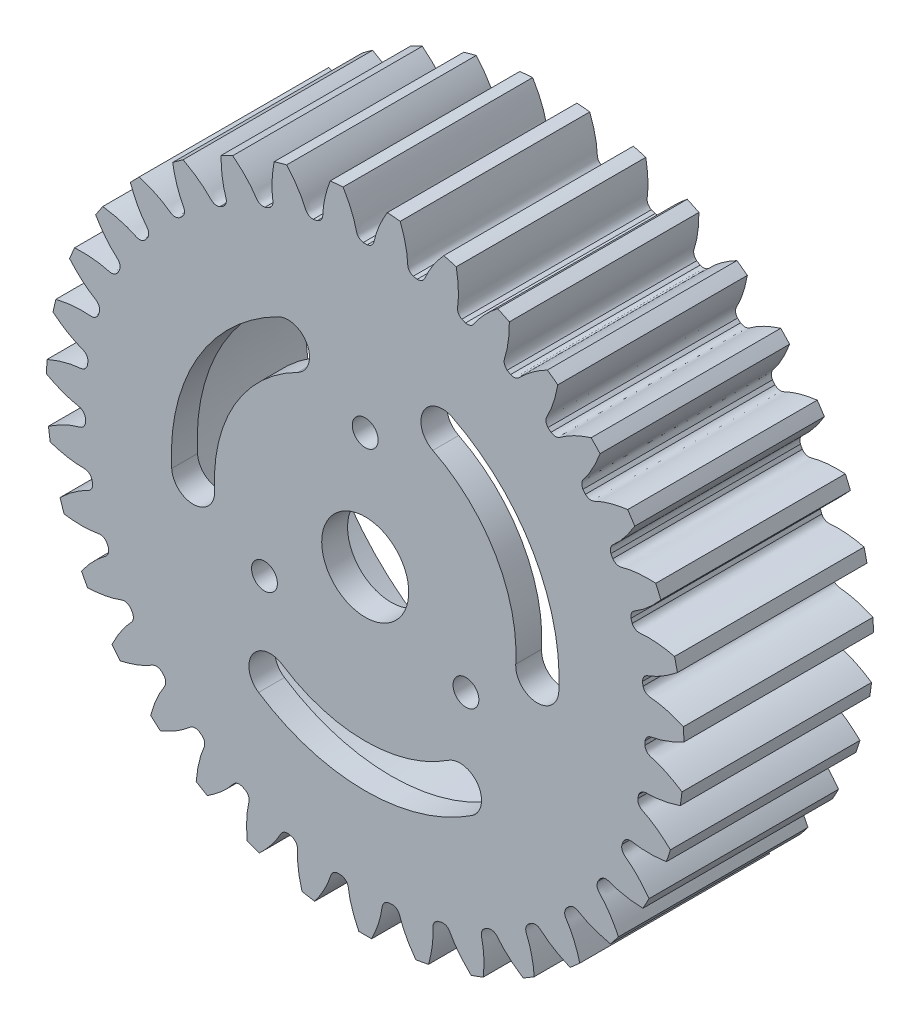
SolidWorks part; units mm, degrees
material "PLA-FC"
ref_plane "前视基准面" through (0, 0, 0) normal (0, 0, 1) x (1, 0, 0)
ref_plane "上视基准面" through (0, 0, 0) normal (0, 1, 0) x (1, 0, 0)
ref_plane "右视基准面" through (0, 0, 0) normal (1, 0, 0) x (0, 0, -1)
sketch "草图1" plane through (0, 0, 0) normal (0, 0, 1) x (1, 0, 0)
  circle A0 centre (0, 0) radius 37
extrude "凸台-拉伸1" add sketch "草图1" along normal blind 50
ref_axis "基准轴1" through (0, 0, -10.5) along (0, 0, 1)
sketch "草图2" plane through (0, 0, 0) normal (0, 0, 1) x (1, 0, 0)
  line L0 (0, 0) -> (0, 37) construction
  circle A0 centre (0, 0) radius 37 construction
  arc A1 (0.2321, 32.4992) -> (-0.2321, 32.4992) centre (0, 0) ccw
  arc A2 (7.1029, 42.1361) -> (-7.1029, 42.1361) centre (0, 0) ccw
  spline S0 degree 3 poles (0.2321, 32.4992) (0.9482, 32.6535) (1.0024, 33.1766) (1.1442, 33.7289) (1.1861, 33.8807) (1.2349, 34.0443) (1.291, 34.2194) (1.3548, 34.4057) (1.4268, 34.6031) (1.5075, 34.8114) (1.5973, 35.0301) (1.6967, 35.259) (1.8062, 35.4979) (1.9261, 35.7464) (2.057, 36.0042) (2.1991, 36.2709) (2.353, 36.5462) (2.519, 36.8297) (2.6975, 37.1211) (2.8889, 37.4199) (3.0935, 37.7258) (3.3117, 38.0383) (3.5439, 38.3571) (3.7904, 38.6816) (4.0515, 39.0114) (4.3275, 39.346) (4.6187, 39.6851) (4.9254, 40.0281) (5.2478, 40.3745) (5.5863, 40.7239) (5.941, 41.0757) (6.4423, 41.5533) (6.834, 41.9044) (7.1029, 42.1361) knots 0 0 0 0 0.117409 0.129436 0.142561 0.156781 0.172098 0.18851 0.206019 0.224624 0.244325 0.265123 0.287016 0.310006 0.334092 0.359274 0.385553 0.412927 0.441398 0.470965 0.501628 0.533387 0.566243 0.600194 0.635242 0.671386 0.708626 0.746962 0.786395 0.826923 0.868548 0.911269 1 1 1 1
  spline S1 degree 3 poles (-0.2321, 32.4992) (-0.9482, 32.6535) (-1.0024, 33.1766) (-1.1442, 33.7289) (-1.1861, 33.8807) (-1.2349, 34.0443) (-1.291, 34.2194) (-1.3548, 34.4057) (-1.4268, 34.6031) (-1.5075, 34.8114) (-1.5973, 35.0301) (-1.6967, 35.259) (-1.8062, 35.4979) (-1.9261, 35.7464) (-2.057, 36.0042) (-2.1991, 36.2709) (-2.353, 36.5462) (-2.519, 36.8297) (-2.6975, 37.1211) (-2.8889, 37.4199) (-3.0935, 37.7258) (-3.3117, 38.0383) (-3.5439, 38.3571) (-3.7904, 38.6816) (-4.0515, 39.0114) (-4.3275, 39.346) (-4.6187, 39.6851) (-4.9254, 40.0281) (-5.2478, 40.3745) (-5.5863, 40.7239) (-5.941, 41.0757) (-6.4423, 41.5533) (-6.834, 41.9044) (-7.1029, 42.1361) knots 0 0 0 0 0.117409 0.129436 0.142561 0.156781 0.172098 0.18851 0.206019 0.224624 0.244325 0.265123 0.287016 0.310006 0.334092 0.359274 0.385553 0.412927 0.441398 0.470965 0.501628 0.533387 0.566243 0.600194 0.635242 0.671386 0.708626 0.746962 0.786395 0.826923 0.868548 0.911269 1 1 1 1
extrude "切除-拉伸1" cut sketch "草图2" along normal through all
pattern_circular "阵列(圆周)1" count 35 every 10.286 about axis through (0, 0, -10.5) along (0, 0, 1) of "切除-拉伸1"
sketch "草图3" plane through (0, 0, 0) normal (0, 0, 1) x (1, 0, 0)
  circle A0 centre (0, 0) radius 35 construction
  dimension "Dn" = 70
sketch "草图4" plane through (0, 0, 0) normal (0, 0, -1) x (-1, 0, 0)
  line L0 (0, 29.928) -> (0, 0) construction
  line L1 (0, 0) -> (26.1668, -15.1074) construction
  circle A0 centre (0, 13.5) radius 1.5
  circle A1 centre (11.6913, -6.75) radius 1.5
  circle A2 centre (-11.6913, -6.75) radius 1.5
  circle A3 centre (0, 0) radius 5.05
  point P13 (0, 0)
  dimension "D2" = 3
  dimension "D5" = 10.1
  dimension "D1" = 120
  dimension "D3" = 13.5
  dimension "D4" = 3
extrude "切除-拉伸2" cut sketch "草图4" against normal through all both and the other way through all
sketch "草图5" plane through (0, 0, 50) normal (0, 0, 1) x (1, 0, 0)
  circle A0 centre (0, 0) radius 45
  dimension "D1" = 90
extrude "切除-拉伸3" cut sketch "草图5" against normal through all from offset 22 offset against normal yes
sketch "草图6" plane through (0, 0, 28) normal (0, 0, -1) x (-1, 0, 0)
  line L0 (0, 0) -> (-20.95, 12.0955) construction
  line L1 (0, 0) -> (0, 13.5) construction
  arc A0 (-19.9655, -1.1746) -> (-8.9655, 17.8779) centre (0, 0) cw construction
  arc A1 (-10.0862, 20.1127) -> (-22.4612, -1.3215) centre (0, 0) ccw
  arc A2 (-7.8448, 15.6432) -> (-17.4698, -1.0278) centre (0, 0) ccw
  arc A3 (-7.8448, 15.6432) -> (-10.0862, 20.1127) centre (-8.9655, 17.8779) ccw
  arc A4 (-22.4612, -1.3215) -> (-17.4698, -1.0278) centre (-19.9655, -1.1746) ccw
  arc A5 (17.4698, -1.0278) -> (7.8448, 15.6432) centre (0, 0) ccw
  arc A6 (17.4698, -1.0278) -> (22.4612, -1.3215) centre (19.9655, -1.1746) ccw
  arc A7 (10.0862, 20.1127) -> (7.8448, 15.6432) centre (8.9655, 17.8779) ccw
  arc A8 (22.4612, -1.3215) -> (10.0862, 20.1127) centre (0, 0) ccw
  arc A9 (8.9655, 17.8779) -> (19.9655, -1.1746) centre (0, 0) cw construction
  arc A10 (-9.625, -14.6154) -> (9.625, -14.6154) centre (0, 0) ccw
  arc A11 (-9.625, -14.6154) -> (-12.375, -18.7912) centre (-11, -16.7033) ccw
  arc A12 (12.375, -18.7912) -> (9.625, -14.6154) centre (11, -16.7033) ccw
  arc A13 (-12.375, -18.7912) -> (12.375, -18.7912) centre (0, 0) ccw
  arc A14 (11, -16.7033) -> (-11, -16.7033) centre (0, 0) cw construction
  point P7 (-17.3205, 10)
  point P17 (17.3205, 10)
  point P24 (0, -20)
  point P29 (0, 0)
  dimension "D2" = 5
  dimension "D3" = 20
  dimension "D1" = 60
  dimension "D4" = 22
extrude "切除-拉伸4" cut sketch "草图6" against normal through all both and the other way through all
sketch "草图7" plane through (0, 0, 28) normal (0, 0, -1) x (-1, 0, 0)
  circle A0 centre (-11.6913, -6.75) radius 4
  circle A1 centre (11.6913, -6.75) radius 4
  circle A2 centre (0, 13.5) radius 4
  dimension "D1" = 8
extrude "切除-拉伸5" cut sketch "草图7" against normal blind 3
sketch "草图8" plane through (0, 0, 28) normal (0, 0, -1) x (-1, 0, 0)
  circle A0 centre (0, 0) radius 29
  dimension "D1" = 58
extrude "切除-拉伸6" cut sketch "草图8" against normal offset from surface (19 mm away) 3 up to face at (0, -17.6641, 50)
move or copy body "实体-移动/复制1" [suppressed] bodies to move or copy 112
move or copy body "实体-移动/复制2" [suppressed] bodies to move or copy 113
